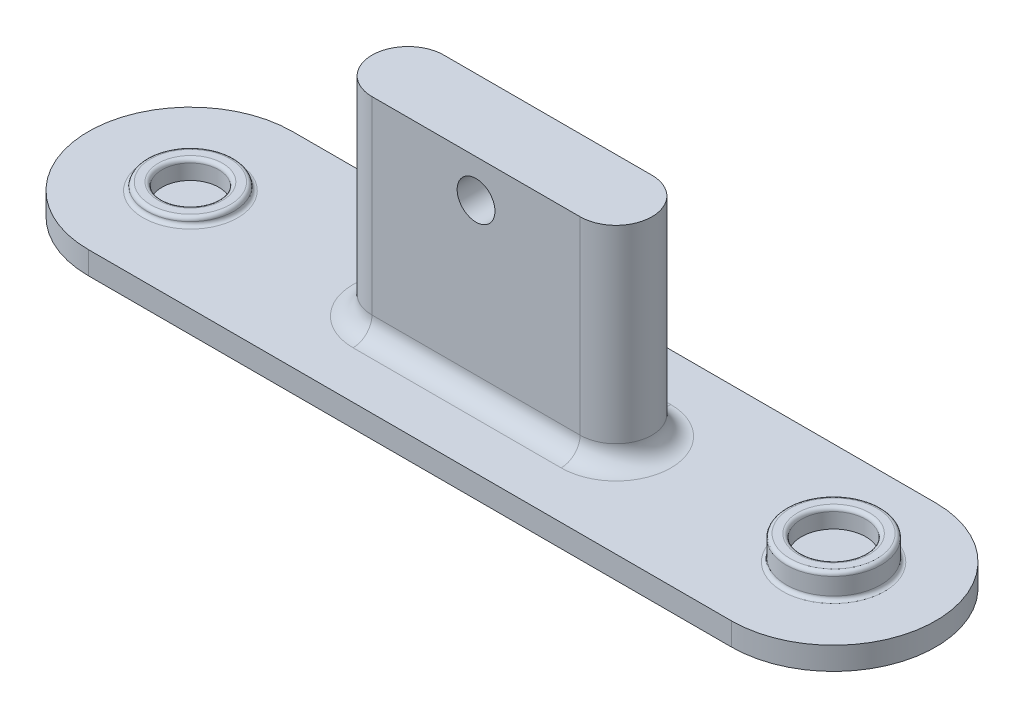
SolidWorks part; units mm, degrees
ref_plane "Front Plane" through (0, 0, 0) normal (0, 0, 1) x (1, 0, 0)
ref_plane "Top Plane" through (0, 0, 0) normal (0, 1, 0) x (1, 0, 0)
ref_plane "Right Plane" through (0, 0, 0) normal (1, 0, 0) x (0, 0, -1)
sketch "Sketch1" plane through (0, 0, 0) normal (0, 1, 0) x (1, 0, 0)
  line L0 (-142.4958, 0) -> (136.0591, 0) construction
  line L1 (0, 82.9006) -> (0, -67.1417) construction
  line L2 (-42.5, -13.5) -> (42.5, -13.5)
  line L3 (-42.5, 13.5) -> (42.5, 13.5)
  arc A0 (-42.5, 13.5) -> (-42.5, -13.5) centre (-42.5, 0) ccw
  arc A1 (42.5, 13.5) -> (42.5, -13.5) centre (42.5, 0) cw
  dimension "D1" = 85
  dimension "D2" = 27
extrude "Boss-Extrude1" add sketch "Sketch1" along normal blind 3
sketch "Sketch7" plane through (0, 3, 0) normal (0, 1, 0) x (1, 0, 0)
  circle A0 centre (-42.5, 0) radius 5.75
  arc A1 (-42.5, 13.5) -> (-42.5, -13.5) centre (-42.5, 0) ccw construction
  dimension "D1" = 11.5
extrude "Boss-Extrude5" add sketch "Sketch7" along normal blind 1
sketch "Sketch2" plane through (0, 4, 0) normal (0, 1, 0) x (1, 0, 0)
  circle A0 centre (-42.5, 0) radius 3.75
  arc A1 (-42.5, 13.5) -> (-42.5, -13.5) centre (-42.5, 0) ccw construction
  dimension "D1" = 7.5
extrude "Cut-Extrude1" cut sketch "Sketch2" against normal blind 2.5
sketch "Sketch3" plane through (0, 3, 0) normal (0, 1, 0) x (1, 0, 0)
  circle A0 centre (42.5, 0) radius 6.25
  arc A1 (42.5, -13.5) -> (42.5, 13.5) centre (42.5, 0) ccw construction
  dimension "D1" = 12.5
extrude "Boss-Extrude3" add sketch "Sketch3" along normal blind 3.25
sketch "Sketch4" plane through (0, 6.25, 0) normal (0, 1, 0) x (1, 0, 0)
  circle A0 centre (42.5, 0) radius 4.25
  circle A1 centre (42.5, 0) radius 6.25 construction
  dimension "D1" = 8.5
extrude "Cut-Extrude2" cut sketch "Sketch4" against normal blind 2.5
sketch "Sketch5" plane through (0, 3, 0) normal (0, 1, 0) x (1, 0, 0)
  line L0 (0, 28.1167) -> (0, -35.5844) construction
  line L1 (-13.75, 4.75) -> (13.75, 4.75)
  line L2 (-13.75, -4.75) -> (13.75, -4.75)
  arc A0 (-13.75, 4.75) -> (-13.75, -4.75) centre (-13.75, 0) ccw
  arc A1 (13.75, 4.75) -> (13.75, -4.75) centre (13.75, 0) cw
  dimension "D1" = 27.5
  dimension "D2" = 9.5
extrude "Boss-Extrude4" add sketch "Sketch5" along normal blind 27.5
sketch "Sketch6" plane through (0, 0, -4.75) normal (0, 0, -1) x (-1, 0, 0)
  line L2 (-13.75, 30.5) -> (13.75, 30.5) construction
  line L3 (0, -7.6238) -> (0, 35.8367) construction
  circle A0 centre (0, 25.5) radius 2.5
  dimension "D1" = 5
  dimension "D2" = 5
extrude "Cut-Extrude3" cut sketch "Sketch6" against normal through all
fillet "Fillet1" radius 0.5 6 edges at (-42.5, 4, 3.75) (-42.5, 4, 5.75) (-42.5, 3, 5.75) (42.5, 6.25, 4.25) (42.5, 6.25, 6.25) (42.5, 3, 6.25)
fillet "Fillet2" radius 2.5 4 edges at (18.5, 3, 0) (0, 3, 4.75) (-18.5, 3, 0) (0, 3, -4.75)
